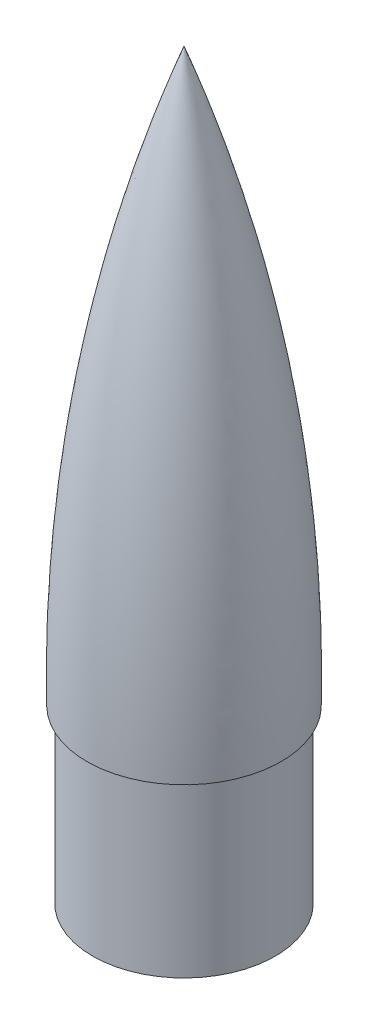
SolidWorks part; units mm, degrees
ref_plane "Спереди" through (0, 0, 0) normal (0, 0, 1) x (1, 0, 0)
ref_plane "Сверху" through (0, 0, 0) normal (0, 1, 0) x (1, 0, 0)
ref_plane "Справа" through (0, 0, 0) normal (1, 0, 0) x (0, 0, -1)
sketch "Эскиз1" plane through (0, 0, 0) normal (0, 1, 0) x (1, 0, 0)
  circle A0 centre (0, 0) radius 15
  circle A1 centre (0, 0) radius 16
  dimension "D1" = 32
  dimension "D2" = 30
extrude "Бобышка-Вытянуть1" add sketch "Эскиз1" along normal blind 30
sketch "Эскиз5" plane through (0, 0, 0) normal (0, 0, 1) x (1, 0, 0)
  line L0 (0, 100) -> (0, 0) construction
  line L1 (0, 30) -> (0, 130)
  line L2 (0, 30) -> (-17, 30)
  line L3 (16, 30) -> (-16, 30) construction
  arc A1 (0, 130) -> (-17, 30) centre (257.5302, 34.7749) ccw
revolve "Повернуть1" add sketch "Эскиз5" angle 360 about L0
sketch "Эскиз6" plane through (0, 0, 0) normal (0, 0, 1) x (1, 0, 0)
  line L2 (0, 128) -> (-1.2853, 123.6776) construction
  line L3 (-1.2853, 123.6776) -> (-2.1438, 120.7719) construction
  line L9 (-2.1438, 120.7719) -> (-6.1212, 103.936) construction
  line L20 (0, 30) -> (0, 130) construction
  line L21 (0, 128) -> (0, 30)
  line L22 (-2, 32) -> (-2, 118.078)
  line L23 (-15.0274, 32) -> (-2, 32)
  line L26 (0, 30) -> (-15, 30)
  line L27 (0, 30) -> (-17, 30) construction
  line L28 (-15.0312, 37.1518) -> (-15.1484, 32.1802) construction
  line L29 (-15.1484, 32.1802) -> (-15, 30) construction
  arc A5 (-2, 118.078) -> (-15.0274, 32) centre (257.5302, 34.7749) ccw
  arc A6 (-6.1212, 103.936) -> (-15.0312, 37.1518) centre (257.5302, 34.7749) ccw
  spline S0 degree 2 poles (-15.0312, 37.1518) (-15.1484, 32.1802) (-15, 30) knots 0 0 0 1 1 1
  spline S1 degree 3 poles (0, 128) (-1.2853, 123.6776) (-2.1438, 120.7719) (-6.1212, 103.936) knots 0 0 0 0 1 1 1 1
  point P0 (0, 128)
  dimension "D2" = 2
  dimension "D3" = 2
  dimension "D1" = 2
revolve "Вырез-Повернуть1" cut sketch "Эскиз6" angle 360 about L21
sketch "Эскиз7" plane through (0, 0, 0) normal (0, 0, 1) x (1, 0, 0)
  line L0 (15.0312, 37.1518) -> (-15.0312, 37.1518) construction
  line L1 (15.0312, 37.1518) -> (-15.0312, 37.1518)
  line L2 (9.0912, 37.1518) -> (9.0912, 45.1518)
  line L3 (14.7699, 45.1518) -> (9.0912, 45.1518)
  line L4 (0, 133.4156) -> (0, -14.3309) construction
  arc A0 (15.0312, 37.1518) -> (14.7699, 45.1518) centre (-107.5812, 37.1518) ccw
  dimension "D1" = 5.94
  dimension "D2" = 8
revolve "Повернуть2" add sketch "Эскиз7" angle 30 about L4 region at (12.0182, 41.122, 0) other way angle 30
sketch "Эскиз11" plane through (0, 0, 0) normal (0, 0, 1) x (1, 0, 0)
  line L0 (9.0912, 37.1518) -> (9.0912, 45.1518) construction
  line L6 (0, -11.3399) -> (0, 84.5532) construction
  line L7 (0, 133.4156) -> (0, -14.3309) construction
  line L8 (-14.7699, 45.1518) -> (-9.0912, 45.1518)
  line L9 (-9.0912, 37.1518) -> (-9.0912, 45.1518)
  line L10 (-15.0312, 37.1518) -> (-9.0912, 37.1518)
  arc A0 (15.0312, 37.1518) -> (14.7699, 45.1518) centre (-107.5812, 37.1518) ccw construction
  arc A2 (-15.0312, 37.1518) -> (-14.7699, 45.1518) centre (107.5812, 37.1518) cw
revolve "Повернуть3" add sketch "Эскиз11" angle 30 about L6 other way angle 30
sketch "Эскиз14" plane through (0, 0, 0) normal (0, 0, 1) x (1, 0, 0)
  line L2 (-15.0574, 35.1518) -> (-15.0312, 37.1518)
  line L3 (-9.0912, 35.1518) -> (-15.0574, 35.1518)
  line L4 (9.0912, 37.1518) -> (9.0912, 35.1518)
  line L5 (9.0912, 35.1518) -> (15.0574, 35.1518)
  line L6 (-15, 0) -> (15, 0) construction
  line L7 (15.0574, 35.1518) -> (15.0312, 37.1518)
  line L8 (0, -7.8263) -> (0, 82.1378) construction
  line L9 (0, 133.4156) -> (0, -14.3309) construction
  line L10 (15.0312, 37.1518) -> (9.0912, 37.1518)
  line L11 (-9.0912, 37.1518) -> (-9.0912, 35.1518)
  line L12 (-15.0312, 37.1518) -> (-9.0912, 37.1518)
  dimension "D1" = 2
revolve "Повернуть4" add sketch "Эскиз14" angle 30 about L8 other way angle 30
sketch "Эскиз17" plane through (0, 35.1518, 0) normal (0, -1, 0) x (1, 0, 0)
  line L0 (0, 27.9011) -> (0, -33.5017) construction
  circle A0 centre (11.72, 0) radius 0.5
  circle A1 centre (-11.72, 0) radius 0.5
  dimension "D1" = 1
  dimension "D2" = 11.72
extrude "Вырез-Вытянуть4" cut sketch "Эскиз17" against normal blind 10
